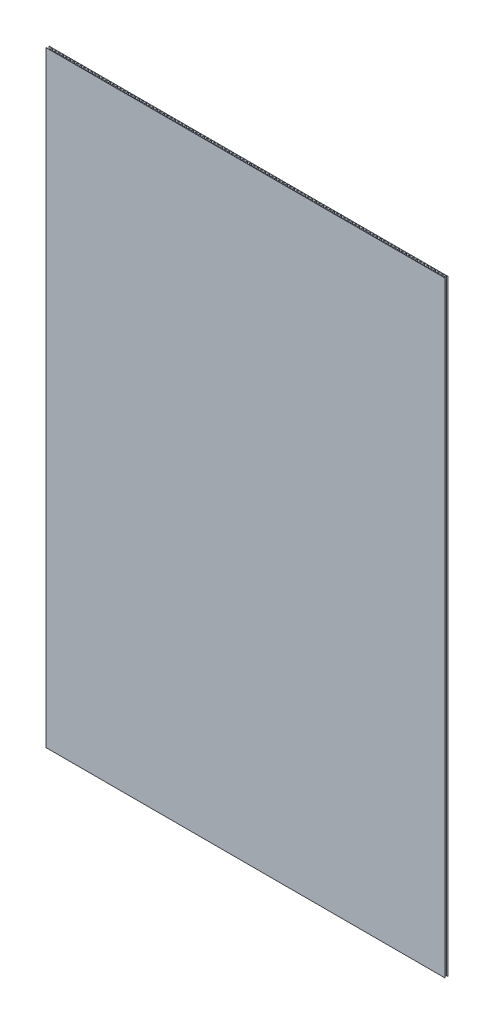
SolidWorks part; units mm, degrees
material "Acrylic (Medium-high impact)"
ref_plane "Front Plane" through (0, 0, 0) normal (0, 0, 1) x (1, 0, 0)
ref_plane "Top Plane" through (0, 0, 0) normal (0, 1, 0) x (1, 0, 0)
ref_plane "Right Plane" through (0, 0, 0) normal (1, 0, 0) x (0, 0, -1)
sketch "Sketch1" plane through (0, 0, 0) normal (0, 1, 0) x (1, 0, 0)
  line L0 (5, -4) -> (-5.3, -4)
  line L1 (-5.3, -4) -> (5, -4) construction
  line L2 (-5, -4) -> (-5, 4) construction
  line L3 (-5.3, 4) -> (5, 4) construction
  line L4 (5, -4) -> (5, 4) construction
  line L5 (-5, -4) -> (5, 4) construction
  line L6 (-5, 4) -> (5, -4) construction
  line L7 (4.7, -3.7) -> (4.7, 3.7)
  line L8 (-5.3, 3.7) -> (4.7, 3.7)
  line L9 (-5.3, -3.7) -> (4.7, -3.7)
  line L10 (5, 4) -> (5, -4)
  line L11 (-5, 4) -> (5, 4) construction
  line L12 (-5, 3.7) -> (5, 3.7) construction
  line L13 (-5, -3.7) -> (5, -3.7) construction
  line L14 (-5, -4) -> (5, -4) construction
  line L15 (5, 4) -> (-5.3, 4)
  line L16 (-5.3, 4) -> (-5.3, -4) construction
  line L17 (-5.3, 4) -> (-5.3, 3.7)
  line L18 (4.7, -4) -> (4.7, 4) construction
  line L19 (-5.3, -3.7) -> (-5.3, -4)
  point P0 (0, 0)
  dimension "D1" = 8
  dimension "D2" = 10
  dimension "D6" = 0.3
  dimension "D3" = 0.3
  dimension "D4" = 0.3
  dimension "D5" = 0.3
extrude "Boss-Extrude1" add sketch "Sketch1" along normal blind 1678
pattern_linear "LPattern1" count 111 spacing 10 along (1, 0, 0) of "Boss-Extrude1"
sketch "Sketch2" plane through (0, 0, 4) normal (0, 0, 1) x (1, 0, 0)
  line L0 (1105, 1678) -> (1105, 0)
  line L1 (1105, 0) -> (1099, 0)
  line L2 (-5.3, 0) -> (1105, 0) construction
  line L3 (1099, 0) -> (1099, 1678)
  line L4 (-5.3, 1678) -> (1105, 1678) construction
  line L5 (1099, 1678) -> (1105, 1678)
  dimension "D1" = 6
extrude "Cut-Extrude1" cut sketch "Sketch2" against normal through all
